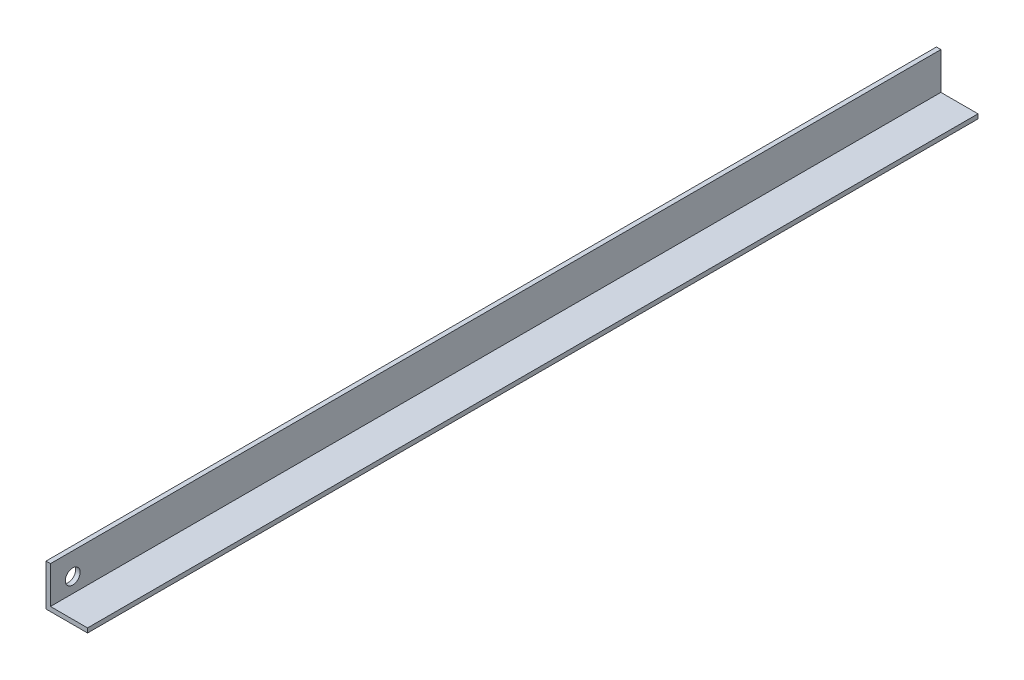
SolidWorks part; units mm, degrees
ref_plane "Спереди" through (0, 0, 0) normal (0, 0, 1) x (1, 0, 0)
ref_plane "Сверху" through (0, 0, 0) normal (0, 1, 0) x (1, 0, 0)
ref_plane "Справа" through (0, 0, 0) normal (1, 0, 0) x (0, 0, -1)
sketch "Эскиз1" plane through (0, 0, 0) normal (0, 0, 1) x (1, 0, 0)
  line L0 (0, 25) -> (0, 0)
  line L1 (0, 0) -> (25, 0)
extrude "Вытянуть-Тонкостенный1" add sketch "Эскиз1" along normal blind 600 thin thin type one direction wall 3
sketch "Эскиз2" plane through (-3, 0, 0) normal (1, 0, 0) x (0, 1, 0)
  circle A0 centre (10, 585) radius 5
extrude "Вырез-Вытянуть3" cut sketch "Эскиз2" along normal blind 10
